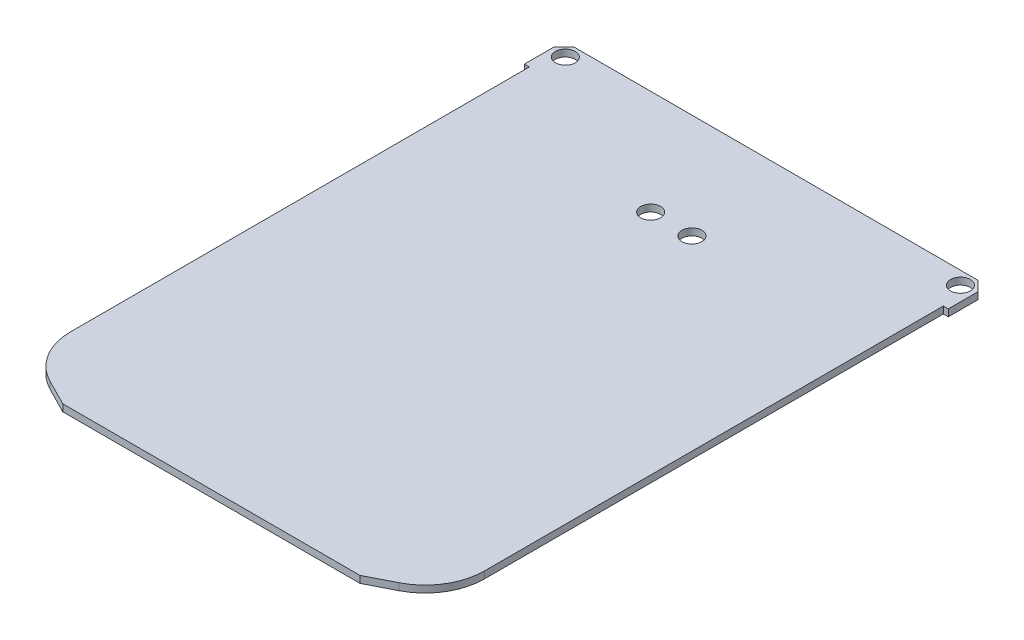
SolidWorks part; units mm, degrees
ref_plane "Front Plane" through (0, 0, 0) normal (0, 0, 1) x (1, 0, 0)
ref_plane "Top Plane" through (0, 0, 0) normal (0, 1, 0) x (1, 0, 0)
ref_plane "Right Plane" through (0, 0, 0) normal (1, 0, 0) x (0, 0, -1)
sketch "Sketch1" plane through (0, 0, 0) normal (0, 1, 0) x (1, 0, 0)
  line L0 (-21.4, 26.5) -> (-20.9, 26.5)
  line L3 (-21.4, 29.5) -> (-21.4, 26.5)
  line L11 (-20.4, 30.5) -> (20.4, 30.5)
  line L17 (0, 30.5) -> (0, -30.5) construction
  line L21 (21.4, 29.5) -> (21.4, 26.5)
  line L22 (21.4, 26.5) -> (20.9, 26.5)
  line L23 (-20.9, 26.5) -> (-20.9, -23.5)
  line L24 (-20.9, -23.5) -> (20.9, -23.5) construction
  line L25 (20.9, -23.5) -> (20.9, 26.5)
  line L26 (-15, -26.5) -> (15, -26.5)
  line L29 (-20.9, -23.5) -> (-15, -26.5)
  line L30 (15, -26.5) -> (20.9, -23.5)
  line L31 (-21.4, 29.5) -> (-20.4, 30.5)
  line L32 (21.4, 29.5) -> (20.4, 30.5)
  circle A6 centre (-19.9444, 29.1814) radius 1
  circle A8 centre (19.9444, 29.1814) radius 1
  point P17 (0, 0)
  point P19 (0, -26.5)
  dimension "D6" = 30.5
  dimension "D9" = 40.8
  dimension "D3" = 29.1814
  dimension "D5" = 45
  dimension "D2" = 19.9444
  dimension "D12" = 2
  dimension "D4" = 50
  dimension "D7" = 35.9
  dimension "D8" = 3
  dimension "D10" = 26.5
  dimension "D11" = 20.9
  dimension "D13" = 0.5
extrude "Boss-Extrude1" add sketch "Sketch1" along normal blind 0.7
sketch "Sketch2" plane through (0, 0.7, 0) normal (0, 1, 0) x (1, 0, 0)
  circle A0 centre (-2.0845, 19.9345) radius 1
  circle A1 centre (2.0845, 19.9345) radius 1
extrude "Cut-Extrude1" cut sketch "Sketch2" against normal blind 4.5
sketch "Sketch3" plane through (0, 0.7, 0) normal (0, 1, 0) x (1, 0, 0)
  line L1 (-9.09, -23.1) -> (-8.69, -23.1) construction
  line L2 (-9.09, -21.43) -> (9.09, -21.43) construction
  line L3 (-9.09, -21.43) -> (-9.09, -23.1) construction
  line L4 (-9.09, -23.1) -> (9.09, -23.1) construction
  line L5 (9.09, -21.43) -> (9.09, -23.1) construction
  line L6 (-9.09, -21.43) -> (9.09, -23.1) construction
  line L7 (-9.09, -23.1) -> (9.09, -21.43) construction
  line L8 (-9.09, -22.13) -> (-9.09, -24.2) construction
  line L9 (9.09, -22.13) -> (9.09, -21.43) construction
  point P0 (9.09, -21.4796)
  point P6 (0, -22.265)
fillet "Fillet1" radius 6 2 edges at (20.9, 0.35, 23.5) (-20.9, 0.35, 23.5)
